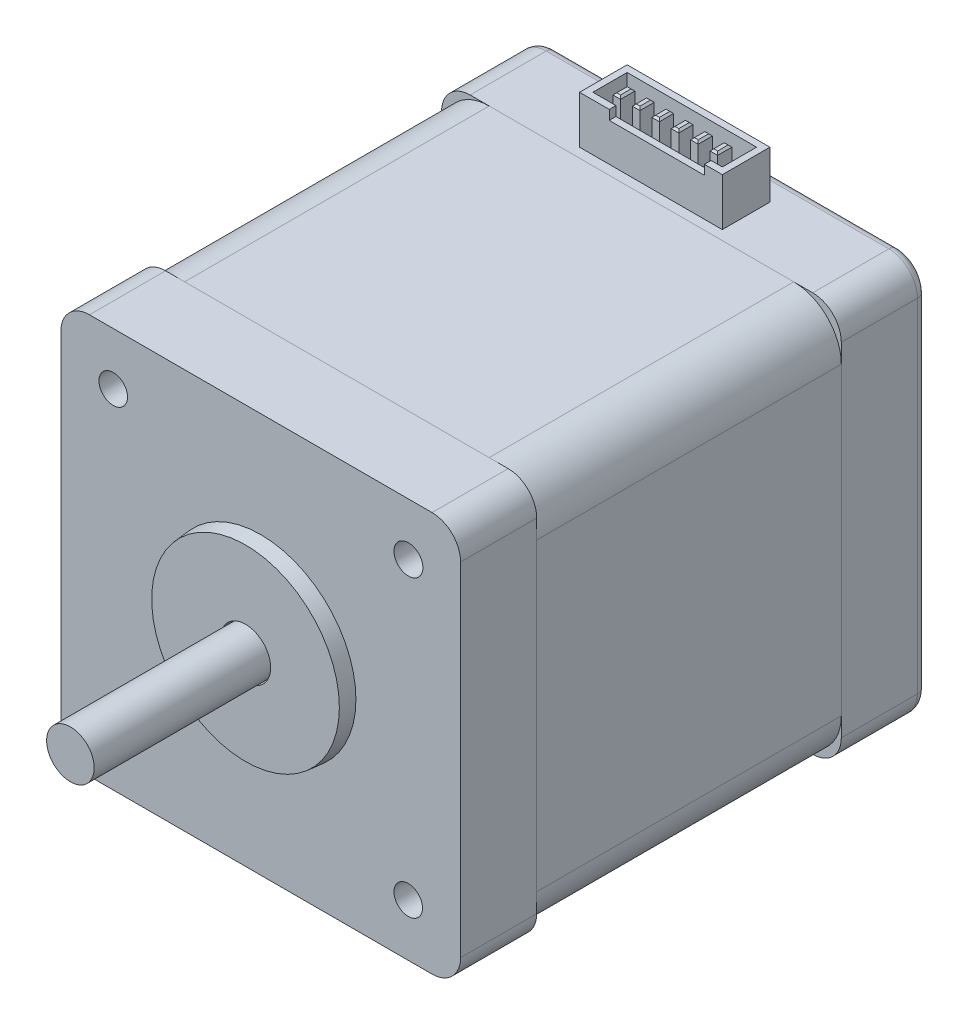
SolidWorks part; units mm, degrees
material "氧化铝"
ref_plane "前视基准面" through (0, 0, 0) normal (0, 0, 1) x (1, 0, 0)
ref_plane "上视基准面" through (0, 0, 0) normal (0, 1, 0) x (1, 0, 0)
ref_plane "右视基准面" through (0, 0, 0) normal (1, 0, 0) x (0, 0, -1)
sketch "草图1" plane through (0, 0, 0) normal (0, 0, 1) x (1, 0, 0)
  line L0 (0, 21) -> (0, -21) construction
  line L1 (-18, 21) -> (18, 21)
  line L2 (-21, 18) -> (-21, -18)
  line L3 (-18, -21) -> (18, -21)
  line L4 (21, 18) -> (21, -18)
  line L5 (-21, 21) -> (21, -21) construction
  line L6 (-21, -21) -> (21, 21) construction
  line L7 (-15.5, 15.5) -> (15.5, 15.5) construction
  line L8 (-15.5, 15.5) -> (-15.5, -15.5) construction
  line L9 (-15.5, -15.5) -> (15.5, -15.5) construction
  line L10 (15.5, 15.5) -> (15.5, -15.5) construction
  line L11 (-15.5, 15.5) -> (15.5, -15.5) construction
  line L12 (-15.5, -15.5) -> (15.5, 15.5) construction
  line L13 (-21, 0) -> (21, 0) construction
  circle A0 centre (-15.5, 15.5) radius 1.5
  circle A1 centre (15.5, 15.5) radius 1.5
  circle A2 centre (15.5, -15.5) radius 1.5
  circle A3 centre (-15.5, -15.5) radius 1.5
  arc A4 (-18, -21) -> (-21, -18) centre (-18, -18) cw
  arc A5 (18, -21) -> (21, -18) centre (18, -18) ccw
  arc A6 (21, 18) -> (18, 21) centre (18, 18) ccw
  arc A7 (-21, 18) -> (-18, 21) centre (-18, 18) cw
  point P0 (0, 0)
  point P6 (0, 0)
  dimension "D4" = 3
  dimension "D5" = 3
  dimension "D1" = 42
  dimension "D2" = 42
  dimension "D3" = 31
extrude "凸台-拉伸1" add sketch "草图1" along normal blind 8
sketch "草图4" plane through (0, 0, 8) normal (0, 0, 1) x (1, 0, 0)
  circle A0 centre (0, 0) radius 2.5
  dimension "D1" = 5
extrude "凸台-拉伸2" add sketch "草图4" along normal blind 20
sketch "草图9" plane through (0, 0, 0) normal (0, 0, -1) x (-1, 0, 0)
  line L1 (-21, 21) -> (21, 21)
  line L2 (-21, 21) -> (-21, -21)
  line L3 (-21, -21) -> (21, -21)
  line L4 (21, 21) -> (21, -21)
  line L5 (-21, 21) -> (21, -21) construction
  line L6 (-21, -21) -> (21, 21) construction
  point P0 (0, 0)
  dimension "D1" = 42
  dimension "D2" = 42
extrude "凸台-拉伸7" add sketch "草图9" along normal blind 32 separate body
sketch "草图10" plane through (0, 0, -32) normal (0, 0, -1) x (-1, 0, 0)
  line L1 (-21, 21) -> (21, 21)
  line L2 (-21, 21) -> (-21, -21)
  line L3 (-21, -21) -> (21, -21)
  line L4 (21, 21) -> (21, -21)
extrude "凸台-拉伸8" add sketch "草图10" along normal blind 9 separate body
fillet "圆角1" radius 3 4 edges at (21, -21, -36.5) (-21, -21, -36.5) (-21, 21, -36.5) (21, 21, -36.5)
fillet "圆角2" radius 5 4 edges at (-21, -21, -16) (-21, 21, -16) (21, 21, -16) (21, -21, -16)
sketch "草图12" plane through (0, 0, 8) normal (0, 0, 1) x (1, 0, 0)
  circle A0 centre (-15.5, 15.5) radius 1.5
  circle A1 centre (15.5185, 15.5) radius 1.5185
  circle A2 centre (-15.5, -15.5) radius 1.5
  circle A3 centre (15.5, -15.5) radius 1.5
extrude "切除-拉伸1" cut sketch "草图12" against normal through all
sketch "草图13" plane through (0, 0, -41) normal (0, 0, -1) x (-1, 0, 0)
  circle A0 centre (0, 0) radius 2.5
extrude "凸台-拉伸9" [suppressed] add sketch "草图13" along normal blind 12
sketch "草图14" plane through (0, 21, 0) normal (0, 1, 0) x (1, 0, 0)
  line L0 (-18, 41) -> (18, 41) construction
  line L1 (-7.5, 38) -> (7.5, 38)
  line L2 (-7.5, 38) -> (-7.5, 33)
  line L3 (-7.5, 33) -> (7.5, 33)
  line L4 (7.5, 38) -> (7.5, 33)
  line L5 (-6.8, 37.3) -> (6.8, 37.3)
  line L6 (6.8, 37.3) -> (6.8, 33.7)
  line L7 (-6.8, 33.7) -> (6.8, 33.7)
  line L8 (-6.8, 37.3) -> (-6.8, 33.7)
  line L9 (-3.66, 36.2073) -> (-2.86, 36.2073)
  line L10 (-5.7, 36.2073) -> (-4.9, 36.2073)
  line L11 (-5.7, 36.2073) -> (-5.7, 34.7073)
  line L12 (-5.7, 34.7073) -> (-4.9, 34.7073)
  line L13 (-4.9, 36.2073) -> (-4.9, 34.7073)
  line L14 (-5.7, 36.2073) -> (-4.9, 34.7073) construction
  line L15 (-5.7, 34.7073) -> (-4.9, 36.2073) construction
  line L16 (-3.66, 36.2073) -> (-3.66, 34.7073)
  line L17 (-3.66, 34.7073) -> (-2.86, 34.7073)
  line L18 (-2.86, 36.2073) -> (-2.86, 34.7073)
  line L19 (-3.66, 36.2073) -> (-2.86, 34.7073) construction
  line L20 (-3.66, 34.7073) -> (-2.86, 36.2073) construction
  line L21 (-1.62, 36.2073) -> (-0.82, 36.2073)
  line L22 (-1.62, 36.2073) -> (-1.62, 34.7073)
  line L23 (-1.62, 34.7073) -> (-0.82, 34.7073)
  line L24 (-0.82, 36.2073) -> (-0.82, 34.7073)
  line L25 (-1.62, 36.2073) -> (-0.82, 34.7073) construction
  line L26 (-1.62, 34.7073) -> (-0.82, 36.2073) construction
  line L27 (0.42, 36.2073) -> (1.22, 36.2073)
  line L28 (0.42, 36.2073) -> (0.42, 34.7073)
  line L29 (0.42, 34.7073) -> (1.22, 34.7073)
  line L30 (1.22, 36.2073) -> (1.22, 34.7073)
  line L31 (0.42, 36.2073) -> (1.22, 34.7073) construction
  line L32 (0.42, 34.7073) -> (1.22, 36.2073) construction
  line L33 (2.46, 36.2073) -> (3.26, 36.2073)
  line L34 (2.46, 36.2073) -> (2.46, 34.7073)
  line L35 (2.46, 34.7073) -> (3.26, 34.7073)
  line L36 (3.26, 36.2073) -> (3.26, 34.7073)
  line L37 (2.46, 36.2073) -> (3.26, 34.7073) construction
  line L38 (2.46, 34.7073) -> (3.26, 36.2073) construction
  line L39 (4.5, 36.2073) -> (5.3, 36.2073)
  line L40 (4.5, 36.2073) -> (4.5, 34.7073)
  line L41 (4.5, 34.7073) -> (5.3, 34.7073)
  line L42 (5.3, 36.2073) -> (5.3, 34.7073)
  line L43 (4.5, 36.2073) -> (5.3, 34.7073) construction
  line L44 (4.5, 34.7073) -> (5.3, 36.2073) construction
  line L45 (0, 41) -> (0, 38) construction
  point P11 (-5.3, 35.4573)
  point P18 (-3.26, 35.4573)
  point P23 (-1.22, 35.4573)
  point P28 (0.82, 35.4573)
  point P33 (2.86, 35.4573)
  point P38 (4.9, 35.4573)
  dimension "D1" = 15
  dimension "D2" = 5
  dimension "D3" = 3
  dimension "D4" = 0.7
  dimension "D5" = 1.5
  dimension "D6" = 0.8
  dimension "D8" = 1.5
  dimension "D9" = 1.5
  dimension "D7" = 6
extrude "凸台-拉伸10" add sketch "草图14" along normal blind 5 contours L4 L1 L2 L3 L8 L5 L6 L7 | L13 L10 L11 L12 | L24 L21 L22 L23 | L42 L39 L40 L41 | L36 L33 L34 L35 | L9 L18 L17 L16 | L27 L30 L29 L28 region at (0, 21, -37.8419) region at (-5.3, 21, -35.4573) region at (-1.22, 21, -35.4573) region at (2.86, 21, -35.4573) region at (4.9, 21, -35.4573)
chamfer "倒角1" distance 0.2 angle 45 24 edges at (4.9, 26, -34.7073) (4.5, 26, -35.4573) (4.9, 26, -36.2073) (5.3, 26, -35.4573) (2.86, 26, -34.7073) (2.46, 26, -35.4573) (2.86, 26, -36.2073) (3.26, 26, -35.4573) (0.82, 26, -36.2073) (1.22, 26, -35.4573) (0.82, 26, -34.7073) (0.42, 26, -35.4573) (-1.22, 26, -34.7073) (-1.62, 26, -35.4573) (-1.22, 26, -36.2073) (-0.82, 26, -35.4573) (-3.26, 26, -36.2073) (-2.86, 26, -35.4573) (-3.26, 26, -34.7073) (-3.66, 26, -35.4573) (-5.3, 26, -34.7073) (-5.7, 26, -35.4573) (-5.3, 26, -36.2073) (-4.9, 26, -35.4573)
sketch "草图15" plane through (0, 0, -33) normal (0, 0, 1) x (1, 0, 0)
  line L0 (0.62, 26) -> (0.62, 22.2151) construction
  line L1 (-4.38, 26) -> (-4.38, 25)
  line L2 (-7.5, 26) -> (7.5, 26) construction
  line L3 (-4.38, 25) -> (5.62, 25)
  line L4 (5.62, 26) -> (5.62, 25)
  line L5 (-4.38, 26) -> (5.62, 26)
  point P9 (0.62, 25)
  dimension "D1" = 5
  dimension "D2" = 1
extrude "切除-拉伸2" cut sketch "草图15" against normal up to next (0.7 mm away)
fillet "圆角3" radius 1 8 edges at (20.1213, 20.1213, -41) (-20.1213, 20.1213, -41) (-21, 0, -41) (-20.1213, -20.1213, -41) (0, -21, -41) (20.1213, -20.1213, -41) (21, 0, -41) (0, 21, -41)
sketch "草图16" plane through (0, 0, 8) normal (0, 0, 1) x (1, 0, 0)
  circle A0 centre (0, 0) radius 10
  circle A1 centre (0, 0) radius 2.5 construction
  circle A2 centre (0, 0) radius 2.5
  dimension "D1" = 20
extrude "凸台-拉伸11" add sketch "草图16" along normal blind 1.6 draft 5
sketch "草图17" plane through (0, 0, -41) normal (0, 0, -1) x (-1, 0, 0)
  circle A0 centre (0, 0) radius 2.5
  dimension "D1" = 5
extrude "凸台-拉伸12" [suppressed] add sketch "草图17" along normal blind 15
sketch "草图18" plane through (0, 0, -41) normal (0, 0, -1) x (-1, 0, 0)
  circle A0 centre (0, 0) radius 5
  dimension "D1" = 10
extrude "切除-拉伸3" cut sketch "草图18" against normal blind 3
sketch "草图19" plane through (0, 0, -38) normal (0, 0, -1) x (-1, 0, 0)
  circle A0 centre (0, 0) radius 2.5
  dimension "D1" = 5
extrude "凸台-拉伸13" add sketch "草图19" along normal blind 2
ref_axis "基准轴1" through (0, 0, 67.221) along (0, 0, -1)
